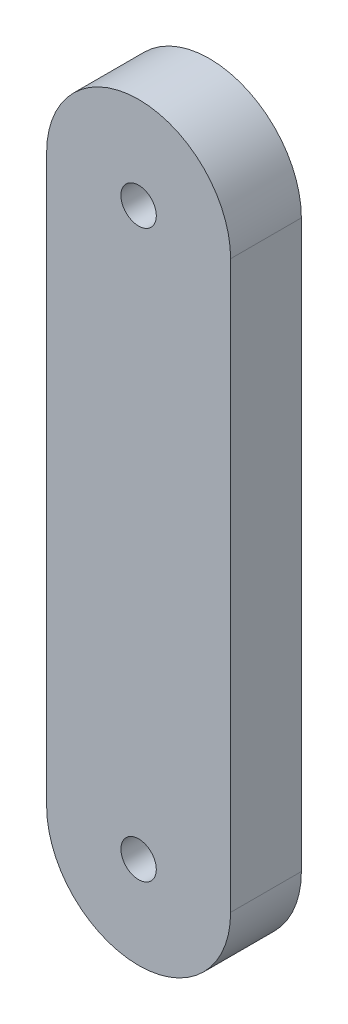
SolidWorks part; units mm, degrees
ref_plane "Front Plane" through (0, 0, 0) normal (0, 0, 1) x (1, 0, 0)
ref_plane "Top Plane" through (0, 0, 0) normal (0, 1, 0) x (1, 0, 0)
ref_plane "Right Plane" through (0, 0, 0) normal (1, 0, 0) x (0, 0, -1)
sketch "Sketch1" plane through (0, 0, 0) normal (0, 0, 1) x (1, 0, 0)
  line L0 (0, 0) -> (0, 20) construction
  line L1 (-3.25, 0) -> (-3.25, 20)
  line L2 (3.25, 0) -> (3.25, 20)
  arc A0 (-3.25, 0) -> (3.25, 0) centre (0, 0) ccw
  arc A1 (3.25, 20) -> (-3.25, 20) centre (0, 20) ccw
  circle A2 centre (0, 20) radius 0.625
  circle A3 centre (0, 0) radius 0.625
  point P2 (0, 10)
  dimension "D2" = 3.25
  dimension "D3" = 1.25
  dimension "D1" = 20
extrude "Boss-Extrude1" add sketch "Sketch1" along normal blind 2.5
